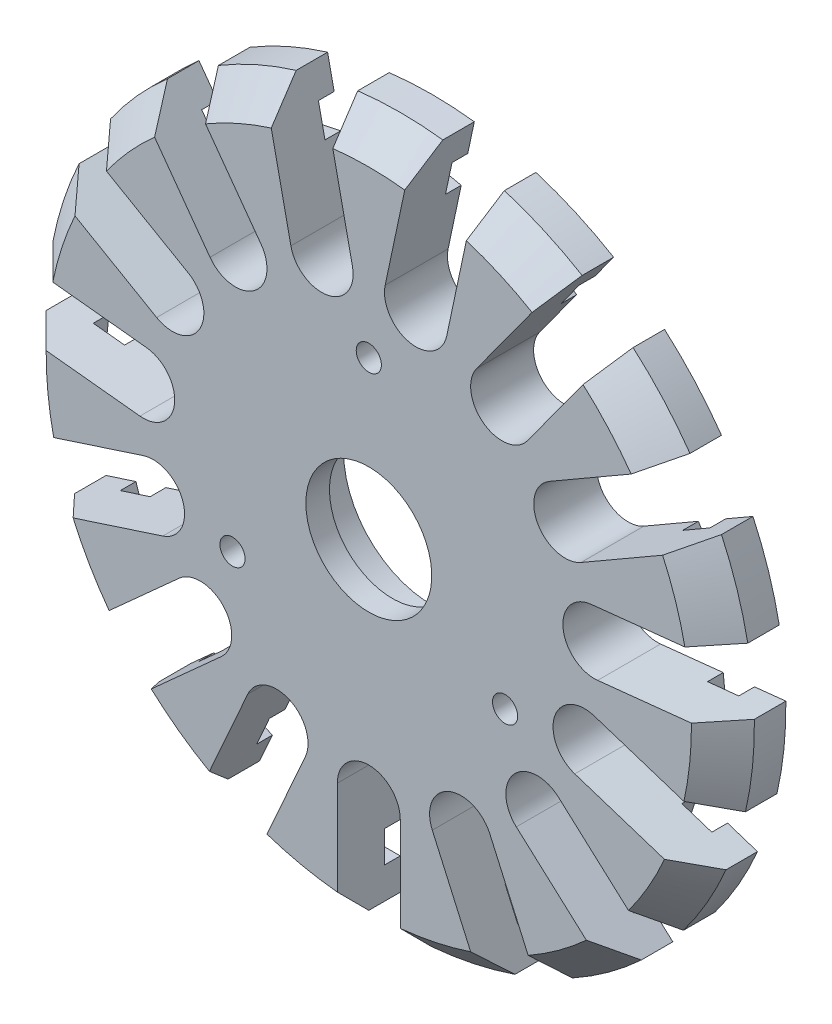
SolidWorks part; units mm, degrees
material "Liga 1060"
ref_plane "Plano frontal" through (0, 0, 0) normal (0, 0, 1) x (1, 0, 0)
ref_plane "Plano superior" through (0, 0, 0) normal (0, 1, 0) x (1, 0, 0)
ref_plane "Plano direito" through (0, 0, 0) normal (1, 0, 0) x (0, 0, -1)
sketch "Esboço1" plane through (0, 0, 0) normal (0, 0, 1) x (1, 0, 0)
  circle A0 centre (0, 0) radius 22.5
  dimension "D1" = 45
extrude "Ressalto-extrusão1" add sketch "Esboço1" along normal blind 4
chamfer "Chanfro1" distance 2 angle 45 1 edges at (22.5, 0, 4)
sketch "Esboço2" plane through (0, 0, 0) normal (0, 0, -1) x (-1, 0, 0)
  line L0 (0, 0) -> (0, 14.4289) construction
  line L1 (2, -22.4109) -> (2, -14.4109)
  line L2 (-2, -22.4109) -> (-2, -14.4109)
  arc A0 (-2, -22.4109) -> (2, -22.4109) centre (0, 0) ccw
  circle A1 centre (0, 0) radius 22.5 construction
  arc A2 (2, -14.4109) -> (-2, -14.4109) centre (0, -14.4109) ccw
  dimension "D1" = 4
  dimension "D2" = 8
extrude "Corte-extrusão1" cut sketch "Esboço2" against normal through all
sketch "Esboço3" plane through (0, 0, 0) normal (0, 0, -1) x (-1, 0, 0)
  circle A0 centre (0, 0) radius 4
  dimension "D1" = 8
extrude "Corte-extrusão2" cut sketch "Esboço3" against normal through all
sketch "Esboço4" plane through (0, 0, 0) normal (0, 0, -1) x (-1, 0, 0)
  circle A0 centre (0, 0) radius 5.6
  dimension "D1" = 11.2
extrude "Corte-extrusão3" cut sketch "Esboço4" against normal blind 2.5
pattern_circular "PadrãoCircular1" count 15 over 360 about axis through (0, 0, 0) along (0, 0, -1) of "Corte-extrusão1"
sketch "Esboço5" plane through (0, 0, 0) normal (0, 0, -1) x (-1, 0, 0)
  circle A0 centre (0, 0) radius 18.5
  circle A1 centre (0, 0) radius 20.5
  dimension "D1" = 41
  dimension "D2" = 37
sketch "Esboço9" plane through (0, 0, 0) normal (0, 0, -1) x (-1, 0, 0)
  line L0 (0, 0) -> (0, 6) construction
  dimension "D1" = 6
sketch "Esboço11" plane through (0, 0, 0) normal (0, 0, -1) x (-1, 0, 0)
  line L0 (0, 0) -> (0, -22.5) construction
  line L1 (2, -22.4109) -> (2, -20.4109) construction
  line L2 (2, -22.4109) -> (2, -14.4109) construction
  line L3 (3.5, -20.4109) -> (-3.5, -20.4109)
  line L4 (-3.5, -20.4109) -> (-3.5, -18.4109)
  line L5 (-3.5, -18.4109) -> (3.5, -18.4109)
  line L6 (3.5, -18.4109) -> (3.5, -20.4109)
  arc A2 (-7.2883, -21.2869) -> (-2, -22.4109) centre (0, 0) ccw construction
  point P13 (0, -20.4109)
  dimension "D1" = 7
  dimension "D2" = 2
  dimension "D3" = 2
extrude "Corte-extrusão4" cut sketch "Esboço11" against normal blind 1
pattern_circular "PadrãoCircular3" count 15 over 360 about axis through (0, 0, 0) along (0, 0, -1) of "Corte-extrusão4"
sketch "Esboço12" plane through (0, 0, 0) normal (0, 0, -1) x (-1, 0, 0)
  circle A0 centre (0, 0) radius 10
  point P3 (0, 10)
  dimension "D1" = 20
hole_wizard "Broca de rosquear para tarraxa de M21" positions "3DSketch2" profile "Esboço14" hole size "M2" standard "ISO" end condition through all
sketch3d "3DSketch2"
  point P0 (0, 10, 0)
sketch "Esboço14" plane through (0, 10, 0) normal (1, 0, 0) x (0, 1, 0)
  line L0 (0, 0) -> (0, 4)
  line L1 (0, 4) -> (0.8, 4)
  line L2 (0.8, 4) -> (0.8, 0)
  line L5 (0.8, 0) -> (0, 0)
  line L11 (0, -6.35) -> (0, 107.95) construction
  dimension "Thru Hole Dia." = 1.6
  dimension "Thru Hole Depth" = 4
pattern_circular "PadrãoCircular4" count 3 over 360 about axis through (0, 0, 0) along (0, 0, -1) of "Broca de rosquear para tarraxa de M21"
